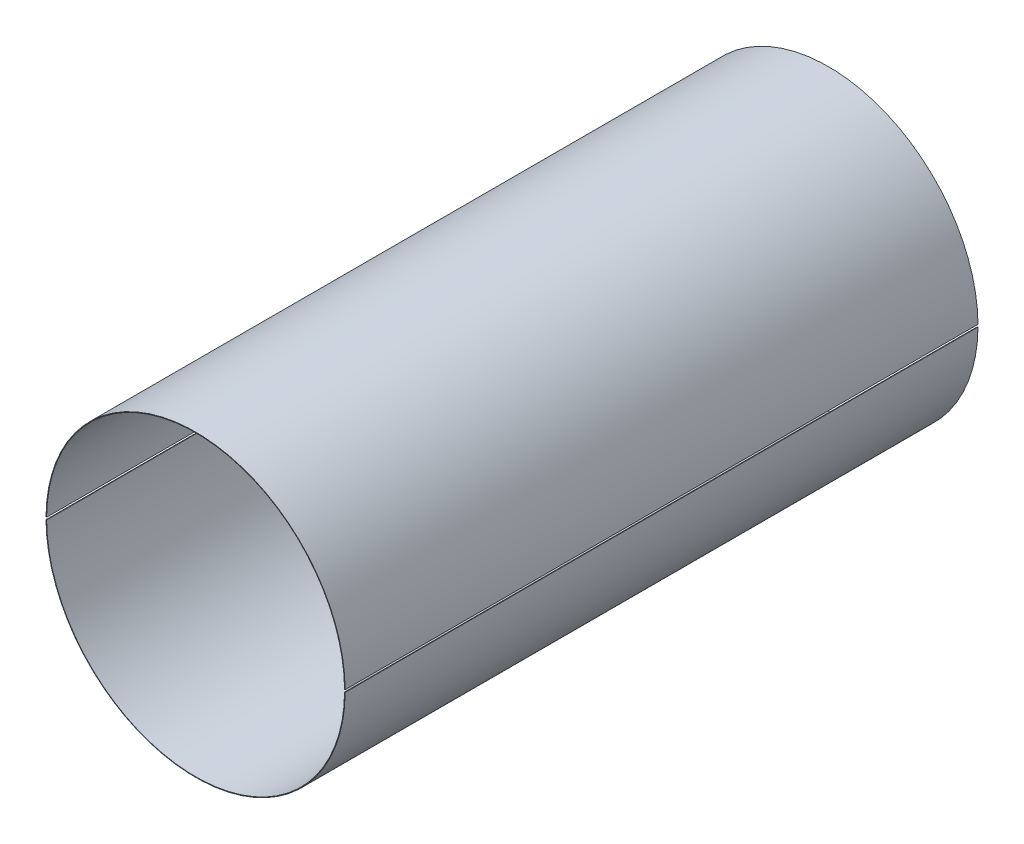
SolidWorks part; units mm, degrees
ref_plane "Front" through (0, 0, 0) normal (0, 0, 1) x (1, 0, 0)
ref_plane "Top" through (0, 0, 0) normal (0, 1, 0) x (1, 0, 0)
ref_plane "Right" through (0, 0, 0) normal (1, 0, 0) x (0, 0, -1)
sketch "Sketch2" plane through (0, 0, 0) normal (0, 0, 1) x (1, 0, 0)
  circle A0 centre (0, 0) radius 66.04
  circle A1 centre (0, 0) radius 65.786
  dimension "D1" = 132.08
  dimension "D2" = 131.572
extrude "Boss-Extrude1" add sketch "Sketch2" along normal blind 279.4
sketch "Sketch3" plane through (0, 0, 279.4) normal (0, 0, 1) x (1, 0, 0)
  line L0 (-71.4518, 0) -> (70.1682, 0) construction
  line L1 (0, 68.3498) -> (0, -67.2802) construction
ref_plane "Plane1" through (-66.04, 0, 0) normal (-1, 0, 0) x (0, 0, 1)
sketch "Sketch5" plane through (-66.04, 0, 0) normal (-1, 0, 0) x (0, 0, 1)
  line L0 (-8.3863, 0) -> (289.133, 0) construction
  line L1 (0, 0.508) -> (279.4, 0.508)
  line L2 (0, 66.04) -> (0, -66.04) construction
  line L3 (279.4, 68.3498) -> (279.4, -67.2802) construction
  line L4 (279.4, 0.508) -> (279.4, -0.508)
  line L5 (0, 0.508) -> (0, -0.508)
  line L6 (0, -0.508) -> (279.4, -0.508)
  point P12 (279.4, 0)
  point P13 (0, 0)
  dimension "D1" = 0.508
extrude "Cut-Extrude1" cut sketch "Sketch5" against normal through all both and the other way through all
